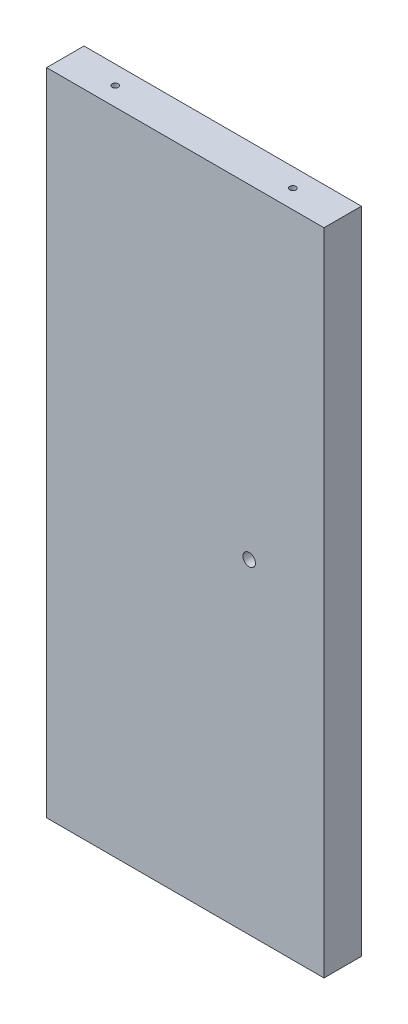
SolidWorks part; units mm, degrees
material "Beech"
ref_plane "Front Plane" through (0, 0, 0) normal (0, 0, 1) x (1, 0, 0)
ref_plane "Top Plane" through (0, 0, 0) normal (0, 1, 0) x (1, 0, 0)
ref_plane "Right Plane" through (0, 0, 0) normal (1, 0, 0) x (0, 0, -1)
sketch "Sketch1" plane through (0, 0, 0) normal (0, 0, 1) x (1, 0, 0)
  line L0 (209.353, -245.4375) -> (209.353, -248.6125) construction
  line L1 (209.353, 93.45) -> (350.6408, 93.45)
  line L2 (209.353, 93.45) -> (209.353, -237.5)
  line L3 (209.353, -237.5) -> (350.6408, -237.5)
  line L4 (350.6408, 93.45) -> (350.6408, -237.5)
  line L6 (209.353, -125) -> (209.353, -144.05) construction
  line L7 (350.6408, 0) -> (350.6408, -19.05) construction
extrude "Boss-Extrude1" add sketch "Sketch1" along normal blind 19.05
hole_wizard "Hole1" positions "Sketch2" profile "Sketch3" legacy
sketch "Sketch2" plane through (196.653, -72.025, 386.2628) normal (-1, 0, 0) x (0, 1, 0)
  point P49 (175, 685.961)
  point P51 (175, 549.8373)
  point P53 (175, 413.7135)
  point P67 (81.55, 779.6497)
  point P73 (81.55, 652.3446)
  point P79 (62.5, 662.9534)
  point P83 (62.5, 769.041)
  point P103 (-62.5, 769.041)
  point P105 (-62.5, 662.9534)
  point P106 (-81.55, 652.3446)
  point P109 (-81.55, 779.6497)
  point P110 (-175, 413.7135)
  point P111 (-175, 549.8373)
  point P112 (-175, 685.961)
  point P115 (-82.7375, 600.3846)
  point P117 (0, 600.3846)
  point P119 (82.7375, 600.3846)
  point P129 (0, 376.7378)
  point P131 (-82.7375, 376.7378)
  point P133 (82.7375, 376.7378)
sketch "Sketch3" plane through (196.653, 102.975, -299.6982) normal (0, 1, 0) x (0, 0, 1)
  line L0 (0, 0) -> (0, 32.7039)
  line L1 (0, 32.7039) -> (1.5875, 31.75)
  line L2 (1.5875, 31.75) -> (1.5875, 4.0177)
  line L3 (1.5875, 4.0177) -> (5.08, 0)
  line L4 (5.08, 0) -> (0, 0)
  line L5 (0, -14.3089) -> (0, 102.4216) construction
  line L6 (0, 32.7039) -> (-1.5875, 31.75) construction
  line L7 (-1.5875, 4.0177) -> (-5.08, 0) construction
  dimension "Diameter" = 3.175
  dimension "Depth" = 31.75
  dimension "C-Sink Diameter" = 10.16
  dimension "C-Sink Angle" = 82
  dimension "Drill Angle" = 118
hole_wizard "Hole3" positions "Sketch6" profile "Sketch7" legacy
sketch "Sketch6" plane through (-181.0394, 112.5, 386.2628) normal (0, 1, 0) x (0.9272, 0, -0.3746)
  line L0 (48.5061, 138.7859) -> (35.9701, 0) construction
  line L5 (414.5728, 105.7206) -> (405.0235, 0) construction
  line L7 (490.0108, 170.6797) -> (621.0107, 117.7523) construction
  line L12 (503.094, 203.0616) -> (634.0938, 150.1342) construction
  line L16 (586.8736, 410.4234) -> (717.8734, 357.496) construction
  line L19 (597.4602, 127.2674) -> (610.5433, 159.6493) construction
  line L20 (610.5433, 159.6493) -> (694.3229, 367.011) construction
  line L22 (513.5613, 161.1647) -> (526.6445, 193.5466) construction
  line L23 (526.6445, 193.5466) -> (610.424, 400.9084) construction
  point P0 (46.2211, 113.4889)
  point P2 (39.3976, 37.9455)
  point P4 (412.2879, 80.4236)
  point P51 (407.3085, 25.297)
  point P56 (513.5613, 161.1647)
  point P58 (597.4602, 127.2674)
  point P61 (610.5433, 159.6493)
  point P63 (694.3229, 367.011)
  point P66 (526.6445, 193.5466)
  point P68 (610.424, 400.9084)
sketch "Sketch7" plane through (-180.6976, 112.5, 263.723) normal (1, 0, 0) x (0, 0, 1)
  line L0 (0, 0) -> (0, 39.0539)
  line L1 (0, 39.0539) -> (1.5875, 38.1)
  line L2 (1.5875, 38.1) -> (1.5875, 4.0177)
  line L3 (1.5875, 4.0177) -> (5.08, 0)
  line L4 (5.08, 0) -> (0, 0)
  line L5 (0, -14.3089) -> (0, 102.4216) construction
  line L6 (0, 39.0539) -> (-1.5875, 38.1) construction
  line L7 (-1.5875, 4.0177) -> (-5.08, 0) construction
  dimension "Diameter" = 3.175
  dimension "Depth" = 38.1
  dimension "C-Sink Diameter" = 10.16
  dimension "C-Sink Angle" = 82
  dimension "Drill Angle" = 118
hole_wizard "1/4 (0.25) Diameter Hole1" positions "Sketch10" profile "Sketch11" hole size "1/4" standard "ANSI Inch" end condition through all
sketch "Sketch10" plane through (0, 0, 0) normal (0, 0, -1) x (-1, 0, 0)
  point P0 (-312.5408, -72.025)
sketch "Sketch11" plane through (312.5408, -72.025, 0) normal (1, 0, 0) x (0, 1, 0)
  line L0 (0, 0) -> (0, 19.05)
  line L1 (0, 19.05) -> (3.175, 19.05)
  line L2 (3.175, 19.05) -> (3.175, 0)
  line L5 (3.175, 0) -> (0, 0)
  line L11 (0, -6.35) -> (0, 107.95) construction
  dimension "Thru Hole Dia." = 6.35
  dimension "Thru Hole Depth" = 19.05
hole_wizard "Hole4" positions "Sketch12" profile "Sketch13" legacy
sketch "Sketch12" plane through (196.653, -72.025, 609.9096) normal (-1, 0, 0) x (0, 1, 0)
  point P49 (175, 685.961)
  point P51 (175, 549.8373)
  point P53 (175, 413.7135)
  point P67 (81.55, 779.6497)
  point P73 (81.55, 652.3446)
  point P79 (62.5, 662.9534)
  point P83 (62.5, 769.041)
  point P103 (-62.5, 769.041)
  point P105 (-62.5, 662.9534)
  point P106 (-81.55, 652.3446)
  point P109 (-81.55, 779.6497)
  point P110 (-175, 413.7135)
  point P111 (-175, 549.8373)
  point P112 (-175, 685.961)
  point P115 (-82.7375, 600.3846)
  point P117 (0, 600.3846)
  point P119 (82.7375, 600.3846)
  point P129 (0, 376.7378)
  point P131 (-82.7375, 376.7378)
  point P133 (82.7375, 376.7378)
sketch "Sketch13" plane through (196.653, 102.975, -76.0514) normal (0, 1, 0) x (0, 0, 1)
  line L0 (0, 0) -> (0, 32.7039)
  line L1 (0, 32.7039) -> (1.5875, 31.75)
  line L2 (1.5875, 31.75) -> (1.5875, 4.0177)
  line L3 (1.5875, 4.0177) -> (5.08, 0)
  line L4 (5.08, 0) -> (0, 0)
  line L5 (0, -14.3089) -> (0, 102.4216) construction
  line L6 (0, 32.7039) -> (-1.5875, 31.75) construction
  line L7 (-1.5875, 4.0177) -> (-5.08, 0) construction
  dimension "Diameter" = 3.175
  dimension "Depth" = 31.75
  dimension "C-Sink Diameter" = 10.16
  dimension "C-Sink Angle" = 82
  dimension "Drill Angle" = 118
hole_wizard "Hole5" positions "Sketch14" profile "Sketch15" legacy
sketch "Sketch14" plane through (-181.0394, 112.5, 609.9096) normal (0, 1, 0) x (0.9272, 0, -0.3746)
  line L0 (48.5061, 138.7859) -> (35.9701, 0) construction
  line L5 (414.5728, 105.7206) -> (405.0235, 0) construction
  line L7 (490.0108, 170.6797) -> (621.0107, 117.7523) construction
  line L12 (503.094, 203.0616) -> (634.0938, 150.1342) construction
  line L16 (586.8736, 410.4234) -> (717.8734, 357.496) construction
  line L19 (597.4602, 127.2674) -> (610.5433, 159.6493) construction
  line L20 (610.5433, 159.6493) -> (694.3229, 367.011) construction
  line L22 (513.5613, 161.1647) -> (526.6445, 193.5466) construction
  line L23 (526.6445, 193.5466) -> (610.424, 400.9084) construction
  point P0 (46.2211, 113.4889)
  point P2 (39.3976, 37.9455)
  point P4 (412.2879, 80.4236)
  point P51 (407.3085, 25.297)
  point P56 (513.5613, 161.1647)
  point P58 (597.4602, 127.2674)
  point P61 (610.5433, 159.6493)
  point P63 (694.3229, 367.011)
  point P66 (526.6445, 193.5466)
  point P68 (610.424, 400.9084)
sketch "Sketch15" plane through (-180.6976, 112.5, 487.3699) normal (1, 0, 0) x (0, 0, 1)
  line L0 (0, 0) -> (0, 39.0539)
  line L1 (0, 39.0539) -> (1.5875, 38.1)
  line L2 (1.5875, 38.1) -> (1.5875, 4.0177)
  line L3 (1.5875, 4.0177) -> (5.08, 0)
  line L4 (5.08, 0) -> (0, 0)
  line L5 (0, -14.3089) -> (0, 102.4216) construction
  line L6 (0, 39.0539) -> (-1.5875, 38.1) construction
  line L7 (-1.5875, 4.0177) -> (-5.08, 0) construction
  dimension "Diameter" = 3.175
  dimension "Depth" = 38.1
  dimension "C-Sink Diameter" = 10.16
  dimension "C-Sink Angle" = 82
  dimension "Drill Angle" = 118
